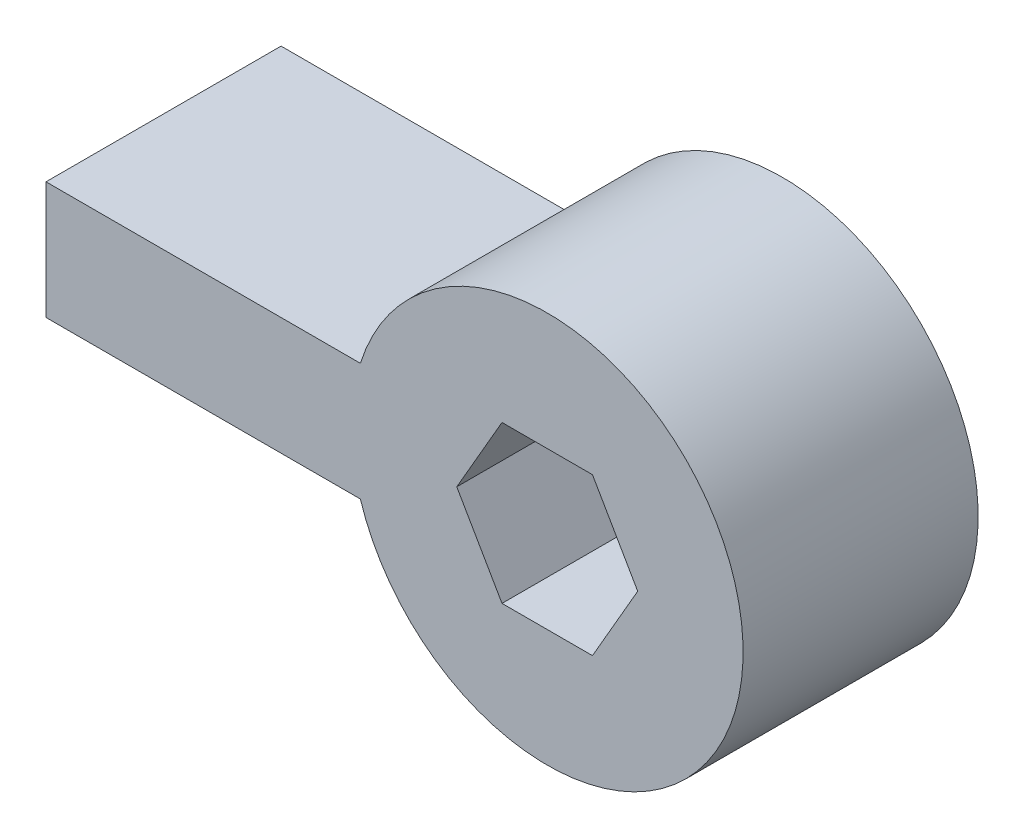
SolidWorks part; units mm, degrees
ref_plane "Front Plane" through (0, 0, 0) normal (0, 0, 1) x (1, 0, 0)
ref_plane "Top Plane" through (0, 0, 0) normal (0, 1, 0) x (1, 0, 0)
ref_plane "Right Plane" through (0, 0, 0) normal (1, 0, 0) x (0, 0, -1)
sketch "Sketch1" plane through (0, 0, 0) normal (0, 0, 1) x (1, 0, 0)
  line L0 (4.3947, 0) -> (6.7041, 0)
  line L1 (5.5494, 0) -> (5.5494, 2) construction
  line L3 (4.3947, 4) -> (3.24, 2)
  line L4 (6.7041, 4) -> (4.3947, 4)
  line L5 (7.8588, 2) -> (6.7041, 4)
  line L6 (6.7041, 0) -> (7.8588, 2)
  line L8 (3.24, 2) -> (4.3947, 0)
  line L9 (1.0426, 5.8059) -> (2.0853, 4) [skipped]
  circle A0 centre (5.5494, 2) radius 5
  point P17 (5.5494, 2)
  dimension "D2" = 4
  dimension "D5" = 10
  dimension "D1" = 6
  dimension "D3" = 4
  dimension "D4" = 4
extrude "Boss-Extrude1" add sketch "Sketch1" along normal blind 6
ref_plane "Plane1" through (0, 2, 0) normal (0, 1, 0) x (1, 0, 0)
sketch "Sketch2" plane through (0, 2, 0) normal (0, 1, 0) x (1, 0, 0)
  line L0 (3.24, 0) -> (0.5494, 0)
  line L2 (0.5494, -6) -> (3.24, -6)
  line L3 (0.5494, -6) -> (10.5494, -6) construction
  line L4 (3.24, -6) -> (3.24, 0)
  line L6 (0.5494, 0) -> (-7.2453, 0)
  line L7 (-7.2453, -6) -> (0.5494, -6)
  line L8 (-7.2453, 0) -> (-7.2453, -6)
extrude "Boss-Extrude2" add sketch "Sketch2" along normal blind 1.5 and the other way blind 1.5
